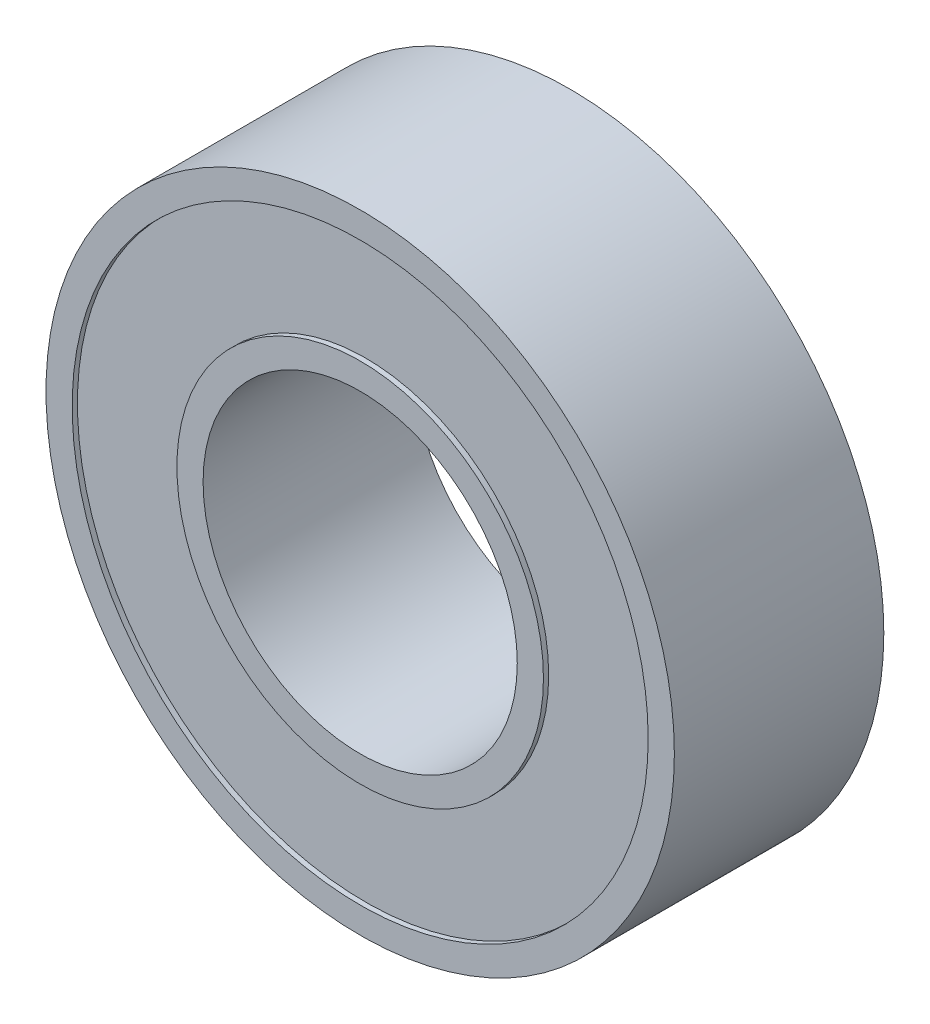
SolidWorks part; units mm, degrees
ref_plane "Front Plane" through (0, 0, 0) normal (0, 0, 1) x (1, 0, 0)
ref_plane "Top Plane" through (0, 0, 0) normal (0, 1, 0) x (1, 0, 0)
ref_plane "Right Plane" through (0, 0, 0) normal (1, 0, 0) x (0, 0, -1)
sketch "Sketch1" plane through (0, 0, 0) normal (0, 0, 1) x (1, 0, 0)
  circle A0 centre (0, 0) radius 6
  circle A1 centre (0, 0) radius 3
  dimension "D1" = 12
  dimension "D2" = 6
extrude "Boss-Extrude1" add sketch "Sketch1" along normal mid plane 4
sketch "Sketch2" plane through (0, 0, 2) normal (0, 0, 1) x (1, 0, 0)
  circle A2 centre (0, 0) radius 5.5
  circle A3 centre (0, 0) radius 5.5
  circle A5 centre (0, 0) radius 3.5
  circle A6 centre (0, 0) radius 3.5
  dimension "D1" = 0.5
  dimension "D2" = 0.5
extrude "Cut-Extrude1" cut sketch "Sketch2" against normal blind 0.1
mirror "Mirror1" about plane through (0, 0, 0) normal (0, 0, 1) of "Cut-Extrude1"
